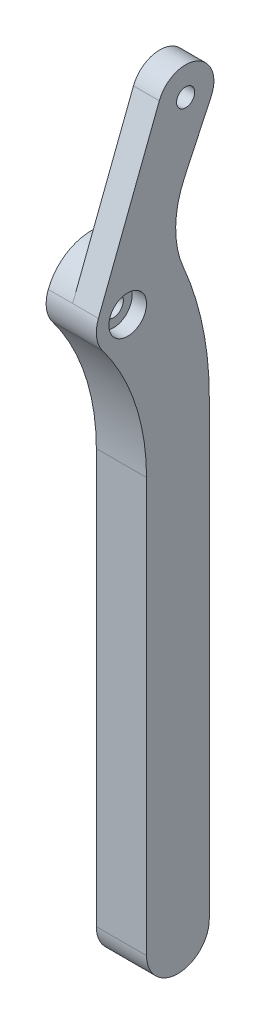
SolidWorks part; units mm, degrees
ref_plane "Front Plane" through (0, 0, 0) normal (0, 0, 1) x (1, 0, 0)
ref_plane "Top Plane" through (0, 0, 0) normal (0, 1, 0) x (1, 0, 0)
ref_plane "Right Plane" through (0, 0, 0) normal (1, 0, 0) x (0, 0, -1)
sketch "Sketch1" plane through (0, 0, 0) normal (1, 0, 0) x (0, 0, -1)
  line L0 (13, -90) -> (13, -17.7993)
  line L1 (5.0352, 26.9888) -> (-4.666, 1.7968)
  line L2 (3, -90) -> (3, -24)
  line L3 (0, 0) -> (9.2345, 25.3717) construction
  line L4 (0, 0) -> (0, 25.3717) construction
  line L5 (0, 25.3717) -> (9.2345, 25.3717) construction
  line L6 (9.0631, 14.4072) -> (13.3088, 23.4611)
  circle A0 centre (0, 0) radius 5
  circle A1 centre (9.2345, 25.3717) radius 4.5
  circle A2 centre (8, -90) radius 5
  arc A3 (3, -24) -> (-4, -3) centre (-32, -24) ccw
  arc A4 (13, -17.7993) -> (8.88, 2.076) centre (-37, -17.7993) ccw
  arc A5 (8.88, 2.076) -> (9.0631, 14.4072) centre (22.644, 8.0386) cw
  circle A6 centre (9.2345, 25.3717) radius 1.45
  circle A7 centre (0, 0) radius 1.6
  arc A8 (8.88, 2.076) -> (-4.666, 1.7968) centre (2.1641, -0.8334) ccw
  dimension "D2" = 9
  dimension "D3" = 10
  dimension "D4" = 10
  dimension "D7" = 15
  dimension "D9" = 50
  dimension "D10" = 35
  dimension "D12" = 2.9
  dimension "D13" = 3.2
  dimension "D1" = 20
  dimension "D5" = 3
  dimension "D6" = 90
  dimension "D8" = 27
  dimension "D11" = 10
extrude "Boss-Extrude1" add sketch "Sketch1" along normal mid plane 8 contours A1 A6 | A5 L6 A1 L1 A0 | A0 A7 | L0 A4 A0 A3 L2 A2 | A2 region at (0, -41.085, -7.5555) region at (0, -90, -8) region at (0, 13.7046, -4.4718) region at (0, 4.7767, -0.888) region at (0, 21.3494, -7.5195)
sketch "Sketch2" plane through (4, 0, 0) normal (1, 0, 0) x (0, 0, -1)
  circle A0 centre (0, 0) radius 3
  dimension "D1" = 6
extrude "Cut-Extrude1" cut sketch "Sketch2" against normal blind 2.3
mirror "Mirror1" about plane through (0, 0, 0) normal (1, 0, 0) of "Cut-Extrude1"
extrude "Cut-Extrude2" cut sketch "Sketch1<5>" against normal through all from offset 0.12 contours A8 A5 L6 A1 L1 | A1 A6 region at (0, 13.7046, -4.4718) region at (0, 21.3494, -7.5195) offset against normal yes
sketch "Sketch1<5>" plane through (0, 0, 0) normal (1, 0, 0) x (0, 0, -1) same geometry as "Sketch1"
move or copy body "Body-Move/Copy1" [suppressed] bodies to move or copy 106
